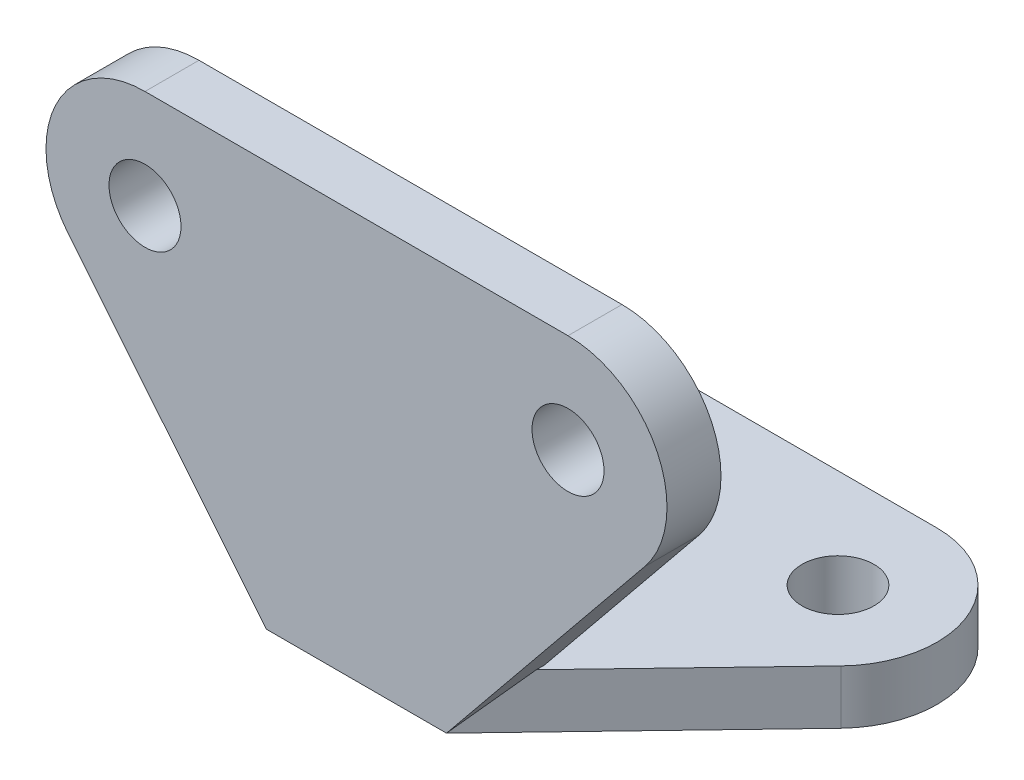
SolidWorks part; units mm, degrees
material "锌 AC41A 合金，作为铸件"
ref_plane "前视基准面" through (0, 0, 0) normal (0, 0, 1) x (1, 0, 0)
ref_plane "上视基准面" through (0, 0, 0) normal (0, 1, 0) x (1, 0, 0)
ref_plane "右视基准面" through (0, 0, 0) normal (1, 0, 0) x (0, 0, -1)
sketch "草图1" plane through (0, 0, 0) normal (0, 1, 0) x (1, 0, 0)
  line L0 (-11.75, 0) -> (11.75, 0) construction
  line L1 (-11.75, 5.5) -> (11.75, 5.5)
  line L2 (15.7222, -3.8042) -> (5, -15)
  line L3 (5, -15) -> (-5, -15)
  line L4 (-5, -15) -> (-15.7222, -3.8042)
  circle A0 centre (-11.75, 0) radius 2
  circle A1 centre (11.75, 0) radius 2
  arc A2 (11.75, 5.5) -> (15.7222, -3.8042) centre (11.75, 0) cw
  arc A3 (-15.7222, -3.8042) -> (-11.75, 5.5) centre (-11.75, 0) cw
  point P4 (0, 0)
  point P17 (0, -15)
  dimension "D1" = 4
  dimension "D4" = 20.5
  dimension "D2" = 23.5
  dimension "D3" = 15
  dimension "D5" = 10
extrude "凸台-拉伸1" add sketch "草图1" along normal blind 3
sketch "草图2" plane through (0, 0, 15) normal (0, 0, 1) x (1, 0, 0)
  line L0 (0, -1000) -> (0, 49000) construction
  line L1 (11.75, 17) -> (-11.75, 17) construction
  line L2 (11.75, 0) -> (-11.75, 0) construction
  line L3 (11.75, 22.5) -> (-11.75, 22.5)
  line L4 (-16.0149, 13.5272) -> (-5, 0)
  line L6 (-5, 0) -> (5, 0)
  line L7 (5, 0) -> (16.0149, 13.5272)
  line L8 (5, 3) -> (5, 0) construction
  line L9 (-15.7222, 0) -> (-5, 0) construction
  circle A0 centre (11.75, 17) radius 2
  circle A1 centre (-11.75, 17) radius 2
  arc A2 (-11.75, 22.5) -> (-16.0149, 13.5272) centre (-11.75, 17) ccw
  arc A3 (16.0149, 13.5272) -> (11.75, 22.5) centre (11.75, 17) ccw
  point P6 (0, 17)
  point P24 (0, 0)
  dimension "D3" = 4
  dimension "D1" = 23.5
  dimension "D2" = 17
  dimension "D4" = 10
  dimension "D5" = 22.5
extrude "凸台-拉伸2" add sketch "草图2" against normal blind 3
sketch "草图3" plane through (0, 0, 0) normal (1, 0, 0) x (0, 0, -1)
  line L0 (-12, 13.5272) -> (-3.8042, 3)
  line L1 (-3.8042, 3) -> (-12, 3)
  line L2 (-12, 3) -> (-12, 13.5272)
extrude "凸台-拉伸3" add sketch "草图3" along normal blind 5 and the other way blind 5
sketch "草图4" plane through (0, 3, 0) normal (0, 1, 0) x (1, 0, 0)
  circle A0 centre (0, -7.9474) radius 2
  dimension "D1" = 4
extrude "切除-拉伸1" cut sketch "草图4" along normal through all
